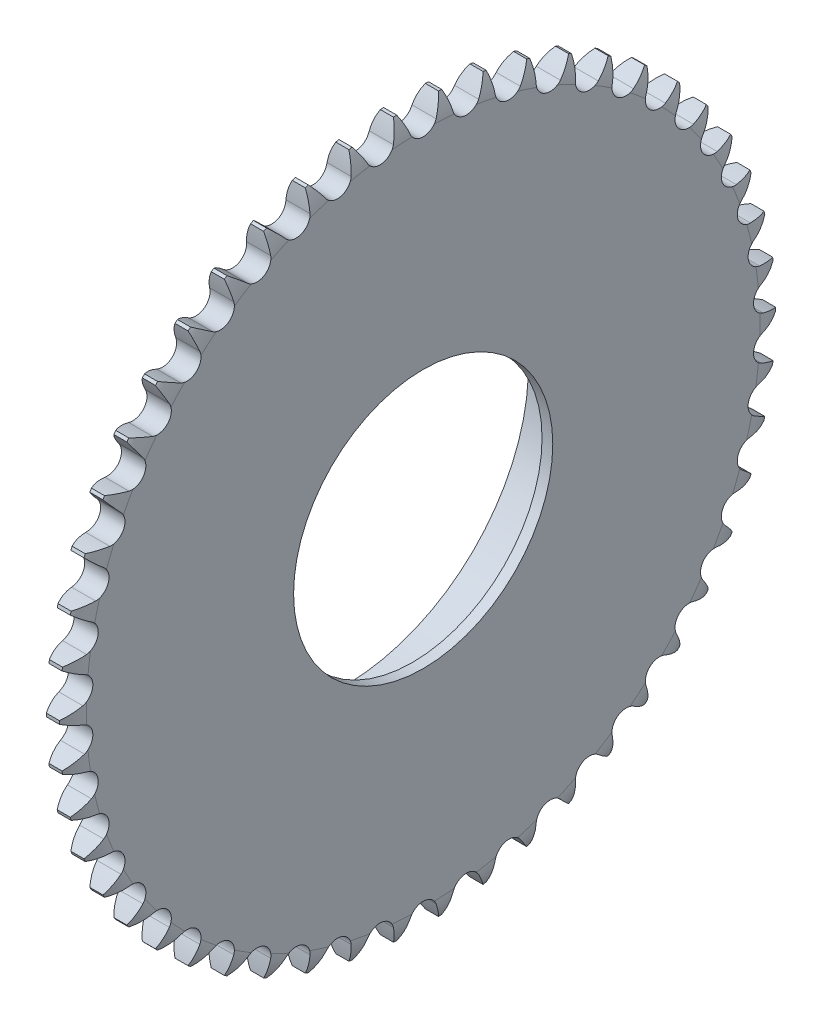
SolidWorks part; units mm, degrees
ref_plane "Plane1" through (0, 0, 0) normal (0, 0, 1) x (1, 0, 0)
ref_plane "Plane2" through (0, 0, 0) normal (0, 1, 0) x (1, 0, 0)
ref_plane "Plane3" through (0, 0, 0) normal (1, 0, 0) x (0, 0, -1)
sketch "Clipboard" plane through (0, 0, 0) normal (0, 1, 0) x (1, 0, 0)
  line L0 (0, 0) -> (10.2043, -12.161)
  line L1 (-15, 0) -> (100, 0) construction
  line L2 (0, 0) -> (-1.3675, 1.5456)
  line L3 (0, 0) -> (-14.8288, 5.6677)
  line L4 (0, 0) -> (1.9926, 2.3747)
  line L5 (0, 0) -> (-23.4238, -8.7364)
  line L6 (0, 0) -> (-7.4026, -4.9946)
  line L7 (-1.3675, 1.5456) -> (14.3658, 20.9747)
  line L8 (-76.2, 38.1) -> (-69.8, 38.1)
  line L9 (-73.5462, 42.5082) -> (-72.9534, 42.6013)
  line L10 (-74, 16.6356) -> (-55.89, 16.6356)
  circle A0 centre (0, 0) radius 5.08
  circle A1 centre (0, 0) radius 60
  circle A2 centre (0, 0) radius 60
  dimension "Num_teeth" = 50
  dimension "Thickness" = 8.93
sketch "BasProSke" plane through (0, 0, 0) normal (0, 1, 0) x (1, 0, 0)
  line L0 (-10, 0) -> (60, 0) construction
  line L1 (0, 0) -> (0, 123.4271)
  line L2 (0, 0) -> (8.93, 0)
  line L3 (8.93, 0) -> (8.93, 123.4271)
  line L4 (6.8662, 131.2543) -> (2.0637, 131.2543)
  arc A0 (0, 123.4271) -> (2.0637, 131.2543) centre (15.875, 123.4271) cw
  arc A1 (8.93, 123.4271) -> (6.8662, 131.2543) centre (-6.945, 123.4271) ccw
  dimension "D1" = 15.875
  dimension "Thickness" = 8.93
  dimension "Diameter" = 262.5085
revolve "Base-Revolve" add sketch "BasProSke" angle 360 about L0
sketch "TooCutSke" plane through (0, 0, 0) normal (1, 0, 0) x (0, 0, -1)
  line L0 (0, 126.4632) -> (4.7932, 124.6328) construction
  line L1 (0, 0) -> (0, 107) construction
  line L2 (0, 126.4632) -> (-10, 126.4632) construction
  line L3 (0, 126.4632) -> (-4.7932, 124.6328) construction
  arc A0 (4.7932, 124.6328) -> (7.9038, 131.517) centre (64.0203, 102.0162) cw
  arc A1 (4.7932, 124.6328) -> (-4.7932, 124.6328) centre (0, 126.4632) cw
  arc A2 (-4.7932, 124.6328) -> (-7.9038, 131.517) centre (-64.0203, 102.0162) ccw
  arc A3 (7.9038, 131.517) -> (-7.9038, 131.517) centre (0, 0) ccw
extrude "ToothCut" cut sketch "TooCutSke" along normal through all
pattern_circular "TeethCuts" count 50 every 7.2 about axis through (-10, 0, 0) along (1, 0, 0) of "ToothCut"
sketch "HubNeaOneSke" plane through (0, 0, 0) normal (-1, 0, 0) x (0, 0, 1)
  circle A0 centre (0, 0) radius 75
  dimension "D1" = 150
extrude "HubNearOne" add sketch "HubNeaOneSke" along normal blind 20
fillet "HubNearOneFillet" radius 0.6 1 edges at (0, 0, -75)
sketch "HubNeaBotSke" plane through (0, 0, 0) normal (-1, 0, 0) x (0, 0, 1)
  circle A0 centre (0, 0) radius 60
  dimension "Diameter" = 120
extrude "HubNearBoth" [suppressed] add sketch "HubNeaBotSke" along normal blind 8.0352
fillet "HubNearBothFillet" [suppressed] radius 0.6
ref_plane "FarPln" through (8.93, 0, 0) normal (1, 0, 0) x (0, 0, -1)
sketch "HubFarSke" plane through (8.93, 0, 0) normal (1, 0, 0) x (0, 0, -1)
  circle A0 centre (0, 0) radius 60
  dimension "Diameter" = 120
extrude "HubFar" [suppressed] add sketch "HubFarSke" along normal blind 8.0352
fillet "HubFarFillet" [suppressed] radius 0.6
sketch "BorSke" plane through (0, 0, 0) normal (1, 0, 0) x (0, 0, -1)
  circle A0 centre (0, 0) radius 47.5
  dimension "Diameter" = 95
extrude "Bore" cut sketch "BorSke" along normal mid plane 50.001
sketch "KeySke" plane through (0, 0, 0) normal (1, 0, 0) x (0, 0, -1)
  line L0 (-14, 0) -> (-14, 53.9)
  line L1 (-14, 53.9) -> (14, 53.9)
  line L2 (14, 53.9) -> (14, 0)
  line L3 (0, 0) -> (0, 34) construction
  line L4 (-14, 0) -> (14, 0)
  dimension "Width" = 28
extrude "Keyway" [suppressed] cut sketch "KeySke" along normal mid plane 50.001
pattern_circular "Keyway2" [suppressed] count 2 every 90 about axis through (-10, 0, 0) along (1, 0, 0) reverse direction yes
sketch "Schizzo1" plane through (-20, 0, 0) normal (-1, 0, 0) x (0, 0, 1)
  circle A0 centre (0, 0) radius 67.5
extrude "Taglio-Estrusione1" cut sketch "Schizzo1" against normal blind 25
ref_plane "Piano1" through (4.465, 0, 0) normal (1, 0, 0) x (0, 0, -1)
sketch "Schizzo2" plane through (4.465, 0, 0) normal (1, 0, 0) x (0, 0, -1)
  circle A1 centre (0, 0) radius 126.46
  dimension "D1" = 252.92
ref_axis "AsseRuota" through (4.465, 0, 0) along (-1, 0, 0)
equation "' \"Pitch@Clipboard\" = 12.7"
equation "' \"Num_strands@Clipboard\" = 1"
equation "' \"Num_teeth@Clipboard\" = 9"
equation "' \"Hub_dia@Clipboard\" = 50"
equation "' \"Overall_len@Clipboard\" = 3"
equation "' \"Diameter@BorSke\" = 12"
equation "' \"T_dim@Clipboard\" = 1"
equation "' \"Width@KeySke\" = 2"
equation "' \"Dr@Clipboard\" = 8.51"
equation "' \"Face_width@Clipboard\" = 7.2"
equation "' \"Side_radius@Clipboard\" = 12.7"
equation "' \"Side_relief@Clipboard\" = 1.27"
equation "' \"Transv_pitch@Clipboard\" = 13.92"
equation "' \"Show_teeth@Clipboard\" = 9"
equation "' \"Fillet_rad@Clipboard\" = 0.6"
equation "' \"Plate_wid@Clipboard\" = 11.8"
equation "\"Num_teeth@Clipboard\" = int( \"Num_teeth@Clipboard\" )"
equation "\"Num_teeth@Clipboard\" = ((sgn( \"Num_teeth@Clipboard\" - 5.0)+1)*( \"Num_teeth@Clipboard\" - 5.0))/2 +5.0"
equation "\"Num_teeth@Clipboard\" = ((sgn( \"Num_teeth@Clipboard\" - 200.0)-1)*( \"Num_teeth@Clipboard\" - 200.0))/-2 +200.0"
equation "\"MHD@Clipboard\" = \"Pitch@Clipboard\" * (1.0 / tan(3.14159265 / \"Num_teeth@Clipboard\" )) - 1.04 * \"Plate_wid@Clipboard\" - 0.76"
equation "\"Thickness@Clipboard\"  = \"Face_width@Clipboard\" + (\"Num_strands@Clipboard\" - 1) * \"Transv_pitch@Clipboard\""
equation "\"OAL@Clipboard\" = \"Thickness@Clipboard\" + 2 * \"Fillet_rad@Clipboard\" + 1"
equation "\"MHD@Clipboard\" = ((sgn( \"MHD@Clipboard\" - \"Hub_dia@Clipboard\" )-1)*( \"MHD@Clipboard\" - \"Hub_dia@Clipboard\" ))/-2+ \"Hub_dia@Clipboard\""
equation "\"OAL@Clipboard\" = ((sgn( \"OAL@Clipboard\" - \"Overall_len@Clipboard\" )+1)*( \"OAL@Clipboard\" - \"Overall_len@Clipboard\" ))/2 + \"Overall_len@Clipboard\" + 0.0005"
equation "\"Num_teeth@TeethCuts\" = int( \"Show_teeth@Clipboard\" ) + 1"
equation "\"Num_teeth@TeethCuts\" = ((sgn( \"Num_teeth@TeethCuts\" - \"Num_teeth@Clipboard\" )-1)*( \"Num_teeth@TeethCuts\" - \"Num_teeth@Clipboard\" ))/-2+ \"Num_teeth@Clipboard\""
equation "\"Num_teeth@TeethCuts\" = ((sgn( \"Num_teeth@TeethCuts\" - 2.0)+1)*( \"Num_teeth@TeethCuts\" - 2.0))/2 +2.0"
equation "\"Angle@TeethCuts\" = 360.0 / \"Num_teeth@Clipboard\""
equation "\"Seat_radius@TooCutSke\" = ( \"Pitch@Clipboard\" / 2.0) / sin(3.14159265 / \"Num_teeth@Clipboard\" ) - \"Dr@Clipboard\" / 2.0 + \"Dr@Clipboard\" * 0.505"
equation "\"R1@TooCutSke\"  = \"Dr@Clipboard\" * 0.505"
equation "\"X@TooCutSke\" = 140.0 - (90.0 / \"Num_teeth@Clipboard\")"
equation "\"R2@TooCutSke\" = 0.12 * \"Dr@Clipboard\" * ( \"Num_teeth@Clipboard\" + 2.0)"
equation "\"Overcut@TooCutSke\" = 0.5 + 0.625 * \"Pitch@Clipboard\" - 0.5 * \"Dr@Clipboard\"  +  \"Pitch@Clipboard\" / 2.0 / sin(3.14159265 / \"Num_teeth@Clipboard\" )"
equation "\"Diameter@BasProSke\" = 2.0 * ( 0.625 * \"Pitch@Clipboard\" - 0.5 * \"Dr@Clipboard\"  +  \"Pitch@Clipboard\" / 2.0 / sin(3.14159265 / \"Num_teeth@Clipboard\" ))"
equation "\"Thickness@BasProSke\"  = \"Thickness@Clipboard\""
equation "\"G1@BasProSke\" =  \"Side_relief@Clipboard\""
equation "\"G2@BasProSke\" =  \"Side_relief@Clipboard\""
equation "\"D1@BasProSke\" =  \"Side_radius@Clipboard\""
equation "\"Diameter@HubNeaBotSke\" = \"MHD@Clipboard\""
equation "\"Length@HubNearBoth\" = ( \"OAL@Clipboard\" - \"Thickness@BasProSke\" ) / 2.0"
equation "\"D1@HubNearOneFillet\" = \"Fillet_rad@Clipboard\""
equation "\"D1@HubNearBothFillet\" = \"Fillet_rad@Clipboard\""
equation "\"Thickness@FarPln\" = \"Thickness@BasProSke\""
equation "\"Diameter@HubFarSke\" = \"MHD@Clipboard\""
equation "\"Length@HubFar\" = ( \"OAL@Clipboard\" - \"Thickness@BasProSke\" ) / 2.0"
equation "\"D1@HubFarFillet\" = \"Fillet_rad@Clipboard\""
equation "\"D1@Bore\" = \"OAL@Clipboard\" * 2.0"
equation "\"D1@Keyway\" = \"OAL@Clipboard\" * 2.0"
equation "\"Offset@KeySke\" = \"T_dim@Clipboard\" + \"Diameter@BorSke\" / 2.0"
